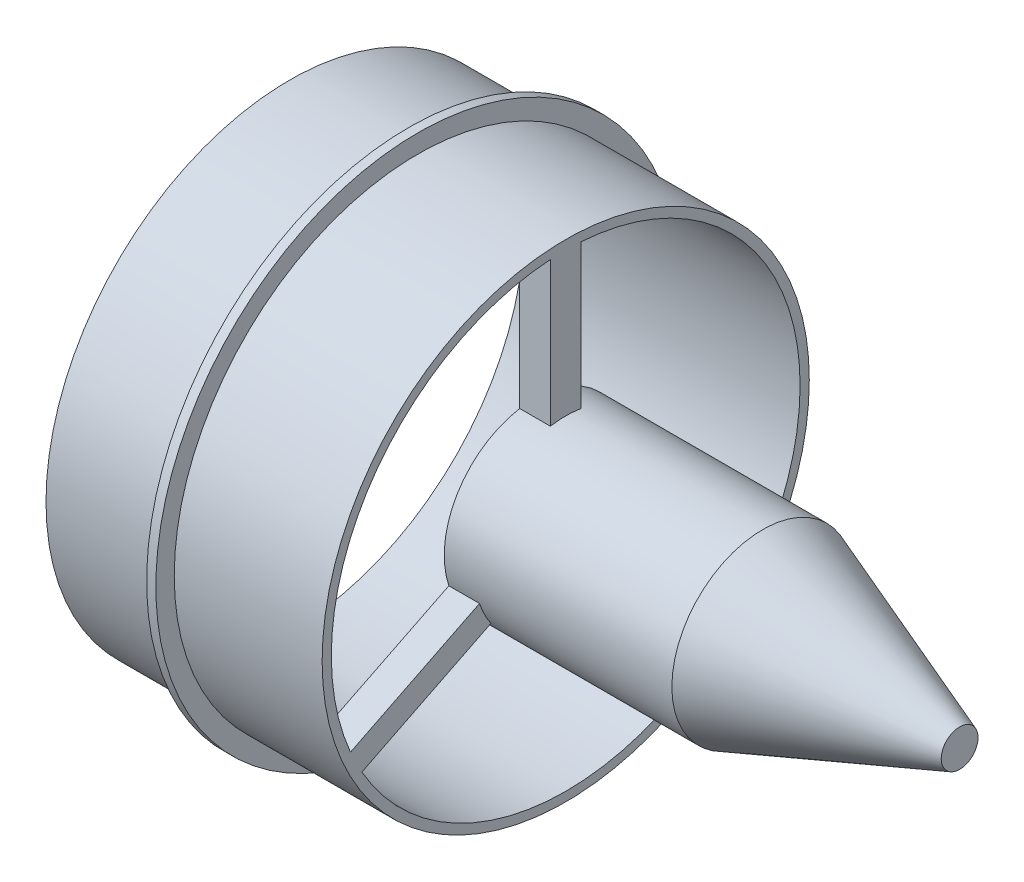
SolidWorks part; units mm, degrees
ref_plane "Спереди" through (0, 0, 0) normal (0, 0, 1) x (1, 0, 0)
ref_plane "Сверху" through (0, 0, 0) normal (0, 1, 0) x (1, 0, 0)
ref_plane "Справа" through (0, 0, 0) normal (1, 0, 0) x (0, 0, -1)
sketch "Эскиз1" plane through (0, 0, 0) normal (1, 0, 0) x (0, 0, -1)
  circle A0 centre (0, 0) radius 39.7
  dimension "D1" = 79.4
extrude "Бобышка-Вытянуть1" add sketch "Эскиз1" along normal blind 45 contours A0
sketch "Эскиз2" plane through (0, 0, 0) normal (-1, 0, 0) x (0, 0, 1)
  circle A0 centre (0, 0) radius 38.2
  dimension "D1" = 76.4
extrude "Вырез-Вытянуть1" cut sketch "Эскиз2" against normal through all
ref_plane "Плоскость4" through (19.4, 0, 0) normal (1, 0, 0) x (0, 0, -1)
sketch "Эскиз3" plane through (19.4, 0, 0) normal (1, 0, 0) x (0, 0, -1)
  circle A0 centre (0, 0) radius 39.7
  circle A1 centre (0, 0) radius 42.7
  dimension "D1" = 85.4
extrude "Бобышка-Вытянуть2" add sketch "Эскиз3" along normal blind 1.5
ref_plane "Плоскость5" through (45, 0, 0) normal (1, 0, 0) x (0, 0, -1)
sketch "Эскиз6" plane through (45, 0, 0) normal (1, 0, 0) x (0, 0, -1)
  line L1 (-2.5, 14.5873) -> (-2.5, 38.1181)
  line L2 (2.5, 14.5873) -> (2.5, 38.1181)
  line L4 (0, -55.0042) -> (0, 38.2) construction
  line L6 (-14.0464, -4.6623) -> (-35.0754, -15.1312)
  line L7 (-12.187, -8.3975) -> (-33.216, -18.8663)
  line L8 (-64.3822, 0) -> (49.2675, 0) construction
  line L9 (12.187, -8.3975) -> (33.216, -18.8663)
  line L10 (14.0464, -4.6623) -> (35.0754, -15.1312)
  arc A0 (-35.0754, -15.1312) -> (-33.216, -18.8663) centre (0, 0) ccw
  arc A1 (-12.187, -8.3975) -> (12.187, -8.3975) centre (0, 0) ccw
  arc A2 (-2.5, 14.5873) -> (-14.0464, -4.6623) centre (0, 0) ccw
  arc A3 (2.5, 38.1181) -> (-2.5, 38.1181) centre (0, 0) ccw
  arc A4 (35.0754, -15.1312) -> (33.216, -18.8663) centre (0, 0) cw
  arc A5 (14.0464, -4.6623) -> (2.5, 14.5873) centre (0, 0) ccw
  dimension "D1" = 76.4
  dimension "D2" = 29.6
  dimension "D3" = 2.5
  dimension "D4" = 2.5
  dimension "D5" = 4.1724
  dimension "D6" = 63.534
  dimension "D7" = 21.029
extrude "Бобышка-Вытянуть3" add sketch "Эскиз6" against normal blind 5
sketch "Эскиз7" plane through (45, 0, 0) normal (1, 0, 0) x (0, 0, -1)
  circle A0 centre (0, 0) radius 14.8
extrude "Бобышка-Вытянуть4" add sketch "Эскиз7" along normal blind 32.1
sketch "Эскиз9" plane through (77.1, 0, 0) normal (1, 0, 0) x (0, 0, -1)
  circle A0 centre (0, 0) radius 14.8
ref_plane "Плоскость6" through (109.2, 0, 0) normal (1, 0, 0) x (0, 0, -1)
sketch "Эскиз10" plane through (109.2, 0, 0) normal (1, 0, 0) x (0, 0, -1)
  circle A0 centre (0, 0) radius 3
  dimension "D1" = 6
loft "По сечениям1" add profiles "Эскиз9", "Эскиз10" connector at (77.1, 0, -14.8) connector at (109.2, 0, -3)
